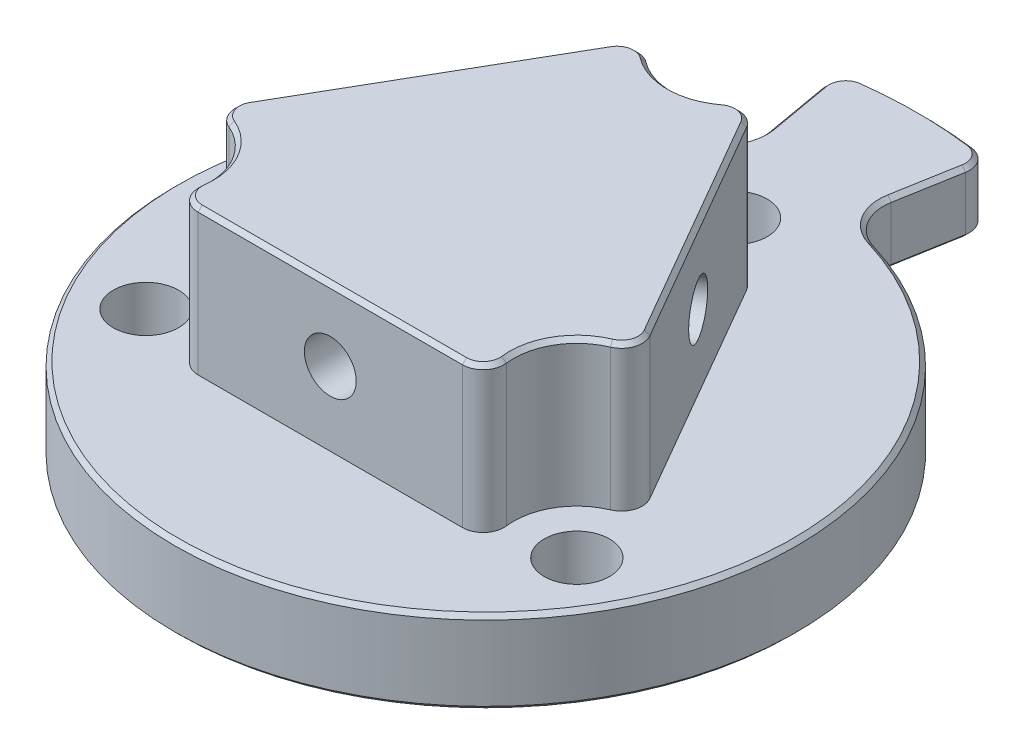
SolidWorks part; units mm, degrees
material "6061 合金"
ref_plane "前视基准面" through (0, 0, 0) normal (0, 0, 1) x (1, 0, 0)
ref_plane "上视基准面" through (0, 0, 0) normal (0, 1, 0) x (1, 0, 0)
ref_plane "右视基准面" through (0, 0, 0) normal (1, 0, 0) x (0, 0, -1)
sketch "草图1" plane through (0, 0, 0) normal (0, 1, 0) x (1, 0, 0)
  circle A0 centre (0, 0) radius 15
  circle A1 centre (0, 0) radius 12 construction
  circle A2 centre (0, 12) radius 1.575
  circle A3 centre (10.3923, -6) radius 1.575
  circle A4 centre (-10.3923, -6) radius 1.575
  point P13 (0, 0)
  dimension "D1" = 30
  dimension "D2" = 24
  dimension "D3" = 3.15
  dimension "D4" = 3
extrude "凸台-拉伸1" add sketch "草图1" along normal blind 4
sketch "草图3" plane through (0, 4, 0) normal (0, 1, 0) x (1, 0, 0)
  line L1 (-7.7942, -7.5) -> (7.7942, -7.5)
  line L2 (10.3923, -3) -> (2.5981, 10.5)
  line L3 (-2.5981, 10.5) -> (-10.3923, -3)
  circle A0 centre (0, 0) radius 15 construction
  circle A1 centre (0, 0) radius 15 construction
  arc A2 (-7.7942, -7.5) -> (-10.3923, -3) centre (-7.7942, -4.5) cw
  arc A3 (7.7942, -7.5) -> (10.3923, -3) centre (7.7942, -4.5) ccw
  arc A4 (2.5981, 10.5) -> (-2.5981, 10.5) centre (0, 9) ccw
  point P12 (-12.9904, -7.5)
  point P15 (12.9904, -7.5)
  point P18 (0, 15)
  dimension "D1" = 3
extrude "凸台-拉伸2" add sketch "草图3" along normal blind 7
ref_axis "基准轴1" through (0, 4, 0) along (0, -1, 0)
sketch "草图8" plane through (0, 11, 0) normal (0, 1, 0) x (1, 0, 0)
  circle A0 centre (-10.3923, -6) radius 3.05
  circle A1 centre (10.3923, -6) radius 3.05
  circle A2 centre (0, 12) radius 3.05
  dimension "D1" = 6.1
  dimension "D2" = 6.1
  dimension "D3" = 6.1
extrude "切除-拉伸3" cut sketch "草图8" against normal offset from surface (7 mm away) 4 up to face at (0, 0, 15)
fillet "圆角4" radius 1 6 edges at (2.6269, 7.5, -10.4501) (-2.6269, 7.5, -10.4501) (-10.3635, 7.5, 2.9501) (-7.7367, 7.5, 7.5) (10.3635, 7.5, 2.9501) (7.7367, 7.5, 7.5)
sketch "草图10" plane through (6.4952, 0, -3.75) normal (0.866, 0, -0.5) x (-0.5, 0, -0.866)
  line L0 (-6.3733, 4) -> (6.3733, 4) construction
  line L3 (0, 11) -> (0, 4) construction
  line L4 (-6.3733, 11) -> (6.3733, 11) construction
  line L5 (15, 4) -> (-15, 4) construction
  circle A0 centre (0, 7.55) radius 1
  dimension "D1" = 2
  dimension "D2" = 3.55
extrude "切除-拉伸4" cut sketch "草图10" against normal blind 5
hole_wizard "M3 螺纹孔1" positions "草图12" profile "草图13" tap size "M3" standard "GB"
sketch "草图12" plane through (6.4952, 0, -3.75) normal (0.866, 0, -0.5) x (-0.5, 0, -0.866)
  point P0 (0, 7.55)
sketch "草图13" plane through (6.4952, 7.55, -3.75) normal (0, 1, 0) x (-0.5, 0, -0.866)
  line L0 (0, 0) -> (0, 5.7511)
  line L1 (0, 5.7511) -> (1.25, 5)
  line L2 (1.25, 5) -> (1.25, 0)
  line L5 (1.25, 0) -> (0, 0)
  line L10 (0, 5.7511) -> (-1.25, 5) construction
  line L11 (0, -6.35) -> (0, 107.95) construction
  dimension "螺纹孔钻头直径" = 2.5
  dimension "螺纹孔钻头深度" = 5
  dimension "导头角度" = 118
cosmetic thread "孔螺纹线1" parameters "D1"=6, "D2"=3
pattern_circular "阵列(圆周)2" count 3 over 360 about axis through (0, 4, 0) along (0, -1, 0) of "切除-拉伸4", "M3 螺纹孔1"
ref_plane "基准面2" through (0, 1, 0) normal (0, -1, 0) x (-1, 0, 0)
sketch "草图20" plane through (0, 1, 0) normal (0, -1, 0) x (-1, 0, 0)
  line L0 (0, 0) -> (-3.6466, 20.681) construction
  line L1 (0, 21) -> (0, 0) construction
  line L2 (0, 0) -> (3.6466, 20.681) construction
  line L3 (-3.6466, 20.681) -> (-2.6047, 14.7721)
  line L4 (3.6466, 20.681) -> (2.6047, 14.7721)
  arc A0 (3.6466, 20.681) -> (-3.6466, 20.681) centre (0, 0) ccw
  circle A1 centre (0, 0) radius 15 construction
  arc A2 (2.6047, 14.7721) -> (-2.6047, 14.7721) centre (0, 0) ccw
  dimension "D1" = 42
  dimension "D2" = 20
extrude "凸台-拉伸3" add sketch "草图20" against normal up to surface (3 mm away) up to face at (0, 4, 15)
fillet "圆角5" radius 1 2 edges at (-3.6466, 2.5, -20.681) (3.6466, 2.5, -20.681)
fillet "圆角7" radius 2 2 edges at (-2.6047, 2.5, -14.7721) (2.6047, 2.5, -14.7721)
chamfer "倒角1" distance 0.2 angle 45 28 edges at (-7.7509, 11, 4.475) (-7.1228, 11, 7.162) (-9.7639, 11, 2.5875) (0, 11, 7.5) (-6.4952, 11, -3.75) (7.1228, 11, 7.162) (-2.6411, 11, -9.7495) (7.7509, 11, 4.475) (0, 11, -8.95) (9.7639, 11, 2.5875) (2.6411, 11, -9.7495) (6.4952, 11, -3.75) (0, 0, 15) (0, 4, 15) (-3.2001, 4, -18.1485) (3.2001, 4, -18.1485) (-3.2884, 4, -20.439) (3.2884, 4, -20.439) (0, 4, -21) (-3.1981, 4, -15.2296) (3.1981, 4, -15.2296) (-3.1981, 1, -15.2296) (3.1981, 1, -15.2296) (-3.2001, 1, -18.1485) (3.2001, 1, -18.1485) (-3.2884, 1, -20.439) (3.2884, 1, -20.439) (0, 1, -21)
sketch "草图14" plane through (0, 0, 0) normal (0, -1, 0) x (1, 0, 0)
  circle A0 centre (0, 0) radius 12 construction
  circle A1 centre (0, 12) radius 1.505
  circle A2 centre (10.3923, -6) radius 1.505
  circle A3 centre (-10.3923, -6) radius 1.505
  point P13 (0, 0)
  dimension "D1" = 3.01
hole_wizard "Ø3.0mm 暗销孔1" positions "草图15" profile "草图16" hole size "Ø3.0" standard "GB"
sketch "草图15" plane through (0, 0, 0) normal (0, -1, 0) x (-1, 0, 0)
  point P0 (-10.3923, 6)
  point P3 (0, -12)
  point P6 (10.3923, 6)
sketch "草图16" plane through (10.3923, 0, -6) normal (1, 0, 0) x (0, 0, -1)
  line L0 (0, 0) -> (0, 3.9013)
  line L1 (0, 3.9013) -> (1.5, 3)
  line L2 (1.5, 3) -> (1.5, 0)
  line L5 (1.5, 0) -> (0, 0)
  line L10 (0, 3.9013) -> (-1.5, 3) construction
  line L11 (0, -6.35) -> (0, 107.95) construction
  dimension "孔直径" = 3
  dimension "孔深度" = 3
  dimension "导头角度" = 118
